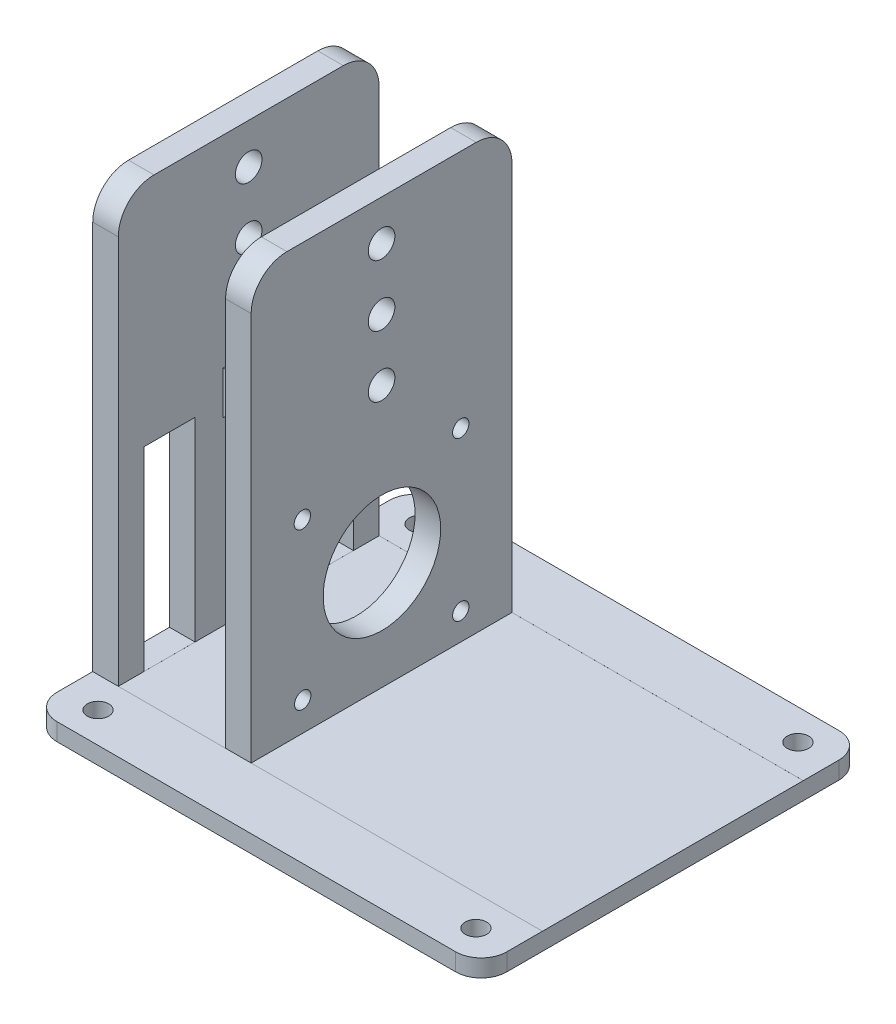
SolidWorks part; units mm, degrees
ref_plane "Front Plane" through (0, 0, 0) normal (0, 0, 1) x (1, 0, 0)
ref_plane "Top Plane" through (0, 0, 0) normal (0, 1, 0) x (1, 0, 0)
ref_plane "Right Plane" through (0, 0, 0) normal (1, 0, 0) x (0, 0, -1)
sketch "Sketch1" plane through (0, 0, 0) normal (0, 1, 0) x (1, 0, 0)
  line L1 (-44.0031, -25.5222) -> (44.0031, -25.5222)
  line L2 (-44.0031, -25.5222) -> (-44.0031, 25.5222)
  line L3 (-44.0031, 25.5222) -> (44.0031, 25.5222)
  line L4 (44.0031, -25.5222) -> (44.0031, 25.5222)
  line L5 (-44.0031, -25.5222) -> (44.0031, 25.5222) construction
  line L6 (-44.0031, 25.5222) -> (44.0031, -25.5222) construction
  point P0 (0, 0)
extrude "Boss-Extrude1" add sketch "Sketch1" along normal blind 3.4061
sketch "Sketch2" plane through (0, 3.4061, 0) normal (0, 1, 0) x (1, 0, 0)
  line L0 (-13.0031, 25.5222) -> (-18.0031, 25.5222)
  line L1 (44.0031, 25.5222) -> (-44.0031, 25.5222) construction
  line L2 (-18.0031, 25.5222) -> (-18.0031, -25.5222)
  line L3 (-44.0031, -25.5222) -> (44.0031, -25.5222) construction
  line L4 (-18.0031, -25.5222) -> (-13.0031, -25.5222)
  line L5 (-13.0031, -25.5222) -> (-13.0031, 25.5222)
  line L6 (-44.0031, 25.5222) -> (-44.0031, -25.5222) construction
  dimension "D1" = 5
  dimension "D2" = 26
extrude "Boss-Extrude3" add sketch "Sketch2" along normal blind 83.1809
sketch "Sketch8" plane through (-13.0031, 0, 0) normal (1, 0, 0) x (0, 0, -1)
  circle A0 centre (0.0714, 24.5561) radius 11.5
extrude "Cut-Extrude3" cut sketch "Sketch8" against normal through all
sketch "Sketch9" plane through (-13.0031, 0, 0) normal (1, 0, 0) x (0, 0, -1)
  circle A0 centre (-15.4286, 9.0561) radius 1.6
  circle A1 centre (-15.5, 39.65) radius 1.6
  circle A2 centre (15.5, 39.65) radius 1.6
  circle A3 centre (15.5, 8.65) radius 1.6
extrude "Cut-Extrude4" cut sketch "Sketch9" against normal through all both and the other way through all
sketch "Sketch17" plane through (-44.0031, -0.0607, 0) normal (-1, 0, 0) x (0, 0, 1)
  line L9 (-25.5222, 0.0607) -> (25.5222, 0.0607)
  line L10 (-25.5222, 0.0607) -> (-25.5222, 86.6476)
  line L11 (-25.5222, 86.6476) -> (25.5222, 86.6476)
  line L12 (25.5222, 0.0607) -> (25.5222, 86.6476)
extrude "Boss-Extrude4" add sketch "Sketch17" against normal blind 5
sketch "Sketch20" plane through (-13.0031, 0, 0) normal (1, 0, 0) x (0, 0, -1)
  circle A0 centre (0, 78.6812) radius 2.605
  circle A1 centre (0, 66.6812) radius 2.605
  circle A2 centre (0, 54.6812) radius 2.605
  point P2 (0, 66.9988)
  point P3 (0, 55.0051)
  dimension "5.2" = 5.21
  dimension "D2" = 5.21
ref_plane "Plane1" through (-39.0031, 86.587, 25.5222) normal (-1, 0, 0) x (0, 0, 1)
fillet "Fillet2" radius 7 1 edges at (-15.5031, 86.587, 25.5222)
fillet "Fillet4" radius 7 1 edges at (-41.5031, 86.587, 25.5222)
fillet "Fillet5" radius 7 1 edges at (-15.5031, 86.587, -25.5222)
fillet "Fillet6" radius 7 1 edges at (-41.5031, 86.587, -25.5222)
sketch "Sketch27" plane through (0, 0, 0) normal (0, -1, 0) x (1, 0, 0)
  line L0 (44.0031, 25.5222) -> (44.0031, -25.5222) construction
  line L1 (-44.0031, -37.5) -> (44.0031, -37.5)
  line L2 (-44.0031, -37.5) -> (-44.0031, -25.5222)
  line L3 (-44.0031, 37.5) -> (44.0031, 37.5)
  line L4 (44.0031, -37.5) -> (44.0031, -25.5222)
  line L5 (-44.0031, -37.5) -> (0, 0) construction
  line L6 (-44.0031, 37.5) -> (-29.9481, 25.5222) construction
  line L7 (-44.0031, 25.5222) -> (44.0031, 25.5222)
  line L9 (44.0031, -25.5222) -> (-44.0031, -25.5222)
  line L11 (-44.0031, 25.5222) -> (-44.0031, 37.5)
  line L12 (0, 0) -> (44.0031, -37.5) construction
  line L13 (29.9481, 25.5222) -> (44.0031, 37.5) construction
  line L14 (44.0031, 25.5222) -> (44.0031, 37.5)
  point P0 (0, 0)
sketch "Sketch28" plane through (0, 3.4061, 0) normal (0, 1, 0) x (1, 0, 0)
  circle A0 centre (36.9756, 31.5111) radius 2.1
  circle A1 centre (-36.9756, 31.5111) radius 2.1
  circle A2 centre (-36.9756, -31.5111) radius 2.1
  circle A3 centre (36.9756, -31.5111) radius 2.1
extrude "Boss-Extrude7" add sketch "Sketch27" against normal blind 3.41
extrude "Cut-Extrude10" cut sketch "Sketch28" against normal through all both and the other way through all
sketch "Sketch29" plane through (-39.0031, 0, 0) normal (1, 0, 0) x (0, 0, -1)
  line L0 (0, 0) -> (0, 86.587)
  line L1 (0.9742, 44.1597) -> (-4.0258, 44.1597)
  line L3 (-4.0258, 47.1046) -> (5, 47.1046)
  line L5 (5, 44.1597) -> (0.9742, 44.1597)
  line L6 (-18.5222, 86.587) -> (18.5222, 86.587) construction
  line L7 (0, 44.1597) -> (-5, 44.1597)
  line L8 (-5, 44.1597) -> (-5, 47.1046)
  line L9 (-5, 47.1046) -> (5, 47.1046)
  line L10 (5, 47.1046) -> (5, 44.1597)
  line L11 (5, 44.1597) -> (0, 44.1597)
fillet "Fillet7" radius 5 4 edges at (44.0031, 1.705, -37.5) (-44.0031, 1.705, -37.5) (-44.0031, 1.705, 37.5) (44.0031, 1.705, 37.5)
extrude "Cut-Extrude12" cut sketch "Sketch20" against normal through all both and the other way through all
extrude "Boss-Extrude10" add sketch "Sketch29" along normal blind 25 contours L10 L3 L0 L1 L5 | L9 L8 L7 L1 L0 L3 region at (-39.0031, 45.6321, 2.5) region at (-39.0031, 45.6321, -2.5)
sketch "Sketch34" plane through (0, 0, 5) normal (0, 0, 1) x (1, 0, 0)
  line L1 (-18.0031, 44.1597) -> (-39.0031, 44.1597) construction
  line L2 (-33.5031, 44.1597) -> (-39.0031, 38.6597)
  line L3 (-39.0031, 141.587) -> (-39.0031, 31.587) construction
  line L4 (-39.0031, 38.6597) -> (-39.0031, 41.6597)
  line L5 (-39.0031, 41.6597) -> (-36.5031, 44.1597)
  line L6 (-36.5031, 44.1597) -> (-33.5031, 44.1597)
  line L8 (-23.6642, 44.1597) -> (-18.0031, 38.4985)
  line L9 (-18.0031, 79.587) -> (-18.0031, 3.41) construction
  line L10 (-18.0031, 38.4985) -> (-18.0031, 41.4985)
  line L11 (-18.0031, 41.4985) -> (-20.6642, 44.1597)
  line L12 (-20.6642, 44.1597) -> (-23.6642, 44.1597)
extrude "Boss-Extrude11" add sketch "Sketch34" against normal blind 10
sketch "Sketch35" plane through (-44.0031, 0, 0) normal (-1, 0, 0) x (0, 0, 1)
  line L3 (-20.5, 41.4985) -> (-10.5, 41.4985)
  line L6 (10.5, 3.41) -> (20.5, 3.41)
  line L9 (-20.5, 3.41) -> (-10.5, 3.41)
  line L11 (10.5, 41.4985) -> (20.5, 41.4985)
  line L12 (20.5, 41.4985) -> (20.5, 3.41)
  line L13 (15.5, 41.4985) -> (20.5, 41.4985)
  line L14 (20.5, 41.4985) -> (10.5, 41.4985)
  line L15 (10.5, 41.4985) -> (10.5, 3.41)
  line L16 (10.5, 3.41) -> (20.5, 3.41)
  line L17 (20.5, 3.41) -> (20.5, 41.4985)
  line L18 (-20.5, 3.41) -> (-20.5, 41.4985)
  line L19 (-10.5, 3.41) -> (-20.5, 3.41)
  line L20 (-10.5, 41.4985) -> (-10.5, 3.41)
  line L21 (-20.5, 41.4985) -> (-10.5, 41.4985)
  line L22 (10.5, 41.4985) -> (20.5, 41.4985)
extrude "Cut-Extrude14" cut sketch "Sketch35" against normal blind 11 contours L11 L15 L6 L12 | L20 L3 L18 L9 region at (-44.0031, 22.4542, -15.5) region at (-44.0031, 22.4542, 15.5)
sketch "Sketch36" plane through (0, 0, 5) normal (0, 0, 1) x (1, 0, 0)
  line L0 (-36.5031, 44.1597) -> (-39.0031, 44.1597)
  line L1 (-39.0031, 141.587) -> (-39.0031, 31.587) construction
  line L2 (-39.0031, 44.1597) -> (-39.0031, 41.6597)
  line L3 (-36.5031, 44.1597) -> (-39.0031, 41.6597) construction
  line L4 (-39.0031, 41.6597) -> (-36.5031, 44.1597)
  line L5 (-20.6642, 44.1597) -> (-18.0031, 44.1597)
  line L6 (-18.0031, 44.1597) -> (-18.0031, 41.4985)
  line L7 (-18.0031, 79.587) -> (-18.0031, 3.41) construction
  line L8 (-18.0031, 41.4985) -> (-20.6642, 44.1597)
extrude "Boss-Extrude12" add sketch "Sketch36" against normal blind 10
